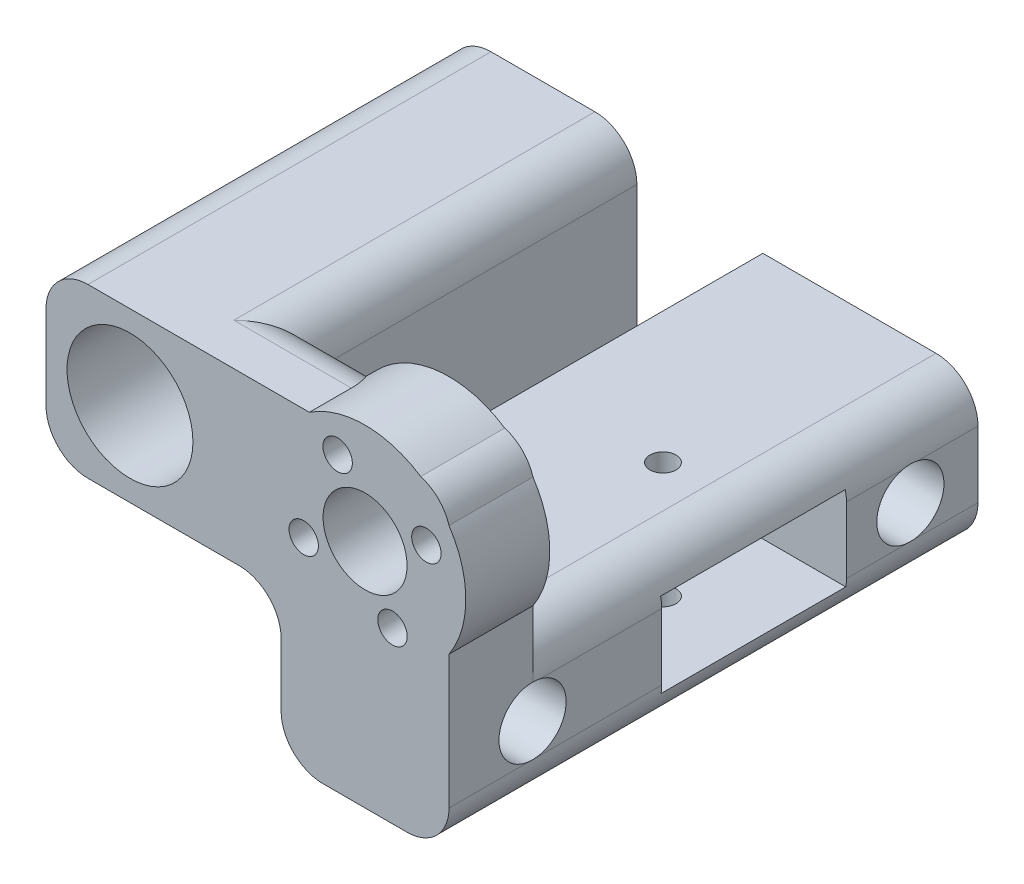
SolidWorks part; units mm, degrees
ref_plane "前视基准面" through (0, 0, 0) normal (0, 0, 1) x (1, 0, 0)
ref_plane "上视基准面" through (0, 0, 0) normal (0, 1, 0) x (1, 0, 0)
ref_plane "右视基准面" through (0, 0, 0) normal (1, 0, 0) x (0, 0, -1)
sketch "草图1" plane through (0, 0, 0) normal (0, 1, 0) x (1, 0, 0)
  line L1 (-10.5078, 7.8964) -> (37.4922, 7.8964)
  line L2 (-10.5078, 7.8964) -> (-10.5078, -40.1036)
  line L3 (-10.5078, -40.1036) -> (37.4922, -40.1036)
  line L4 (37.4922, 7.8964) -> (37.4922, -40.1036)
  line L5 (-10.5078, 7.8964) -> (37.4922, -40.1036) construction
  line L6 (-10.5078, -40.1036) -> (37.4922, 7.8964) construction
  point P4 (13.4922, -16.1036)
  dimension "D1" = 48
  dimension "D2" = 48
extrude "凸台-拉伸1" add sketch "草图1" along normal blind 40
sketch "草图2" plane through (0, 0, 40.1036) normal (0, 0, 1) x (1, 0, 0)
  line L0 (-10.5078, 40) -> (37.4922, 40) construction
  line L1 (-10.5078, 40) -> (-10.5078, 0) construction
  circle A0 centre (-0.5078, 30) radius 7.5
  circle A1 centre (27.4922, 30) radius 5
  circle A2 centre (24.2267, 37.3032) radius 1.75
  circle A3 centre (34.7954, 33.2656) radius 1.75
  circle A4 centre (20.1891, 26.7344) radius 1.75
  circle A5 centre (30.7578, 22.6968) radius 1.75
  dimension "D1" = 15
  dimension "D2" = 10
  dimension "D4" = 10
  dimension "D5" = 10
  dimension "D3" = 28
extrude "切除-拉伸1" cut sketch "草图2" against normal through all
sketch "草图3" plane through (0, 0, 40.1036) normal (0, 0, 1) x (1, 0, 0)
  circle A0 centre (27.4922, 30) radius 12
  circle A1 centre (27.4922, 30) radius 5.5
  circle A2 centre (24.2267, 37.3032) radius 1.75
  circle A3 centre (20.1891, 26.7344) radius 1.75
  circle A4 centre (30.7578, 22.6968) radius 1.75
  circle A5 centre (34.7954, 33.2656) radius 1.75
  dimension "D1" = 24
  dimension "D2" = 11
extrude "凸台-拉伸3" add sketch "草图3" against normal blind 10
sketch "草图4" plane through (0, 0, -7.8964) normal (0, 0, -1) x (-1, 0, 0)
  line L1 (-37.4922, 40) -> (-11.8688, 40)
  line L2 (-37.4922, 40) -> (-37.4922, 20.3994)
  line L3 (-37.4922, 20.3994) -> (-11.8688, 20.3994)
  line L4 (-11.8688, 40) -> (-11.8688, 20.3994)
  line L5 (-37.4922, 40) -> (-11.8688, 20.3994) construction
  line L6 (-37.4922, 20.3994) -> (-11.8688, 40) construction
  point P4 (-24.6805, 30.1997)
extrude "切除-拉伸2" cut sketch "草图4" against normal blind 38
fillet "圆角1" radius 5 1 edges at (37.4922, 40, 35.1036)
sketch "草图5" plane through (37.4922, 0, 0) normal (1, 0, 0) x (0, 0, -1)
  line L1 (-14.7696, 16.6006) -> (7.2304, 16.6006)
  line L2 (-14.7696, 16.6006) -> (-14.7696, 6.6006)
  line L3 (-14.7696, 6.6006) -> (7.2304, 6.6006)
  line L4 (7.2304, 16.6006) -> (7.2304, 6.6006)
  line L5 (-14.7696, 16.6006) -> (7.2304, 6.6006) construction
  line L18 (-14.7696, 6.6006) -> (7.2304, 16.6006) construction
  point P10 (0.3003, 11.5442)
  dimension "D1" = 10
  dimension "D2" = 22
extrude "切除-拉伸3" cut sketch "草图5" against normal through all
sketch "草图6" plane through (0, 0, 40.1036) normal (0, 0, 1) x (1, 0, 0)
  line L0 (37.4922, 0) -> (37.4922, 2.5)
  line L1 (37.4922, 23.3668) -> (37.4922, 0) construction
  line L2 (-7.5078, 2.5) -> (392.4922, 2.5) construction
  line L3 (37.4922, 2.5) -> (17.4922, 2.5)
  line L4 (17.4922, 2.5) -> (17.4922, 20)
  line L5 (17.4922, 20) -> (-10.5078, 20)
  line L6 (-10.5078, 40) -> (-10.5078, 0) construction
  line L7 (-10.5078, 20) -> (-10.5078, 0)
  line L8 (-10.5078, 0) -> (37.4922, 0)
  dimension "D1" = 20
  dimension "D2" = 20
extrude "切除-拉伸4" cut sketch "草图6" against normal through all
fillet "圆角2" radius 5 7 edges at (16.3639, 40, 30.1036) (11.8688, 40, 11.1036) (37.4922, 2.5, 16.1036) (-10.5078, 40, 16.1036) (-10.5078, 20, 16.1036) (17.4922, 2.5, 16.1036) (17.4922, 20, 16.1036)
sketch "草图7" plane through (17.4922, 0, 0) normal (-1, 0, 0) x (0, 0, 1)
  line L0 (-7.8964, 20) -> (-7.8964, 2.5)
  line L1 (-7.8964, 2.5) -> (1.8729, 2.5)
  line L2 (40.1036, 2.5) -> (-7.8964, 2.5) construction
  line L3 (1.8729, 2.5) -> (1.8729, 20)
  line L4 (40.1036, 20) -> (-7.8964, 20) construction
  line L5 (1.8729, 20) -> (-7.8964, 20)
extrude "凸台-拉伸4" add sketch "草图7" along normal blind 23
fillet "圆角3" radius 5 3 edges at (17.4922, 2.5, -3.0117) (-5.5078, 20, -3.0117) (-5.5078, 2.5, -3.0117)
fillet "圆角4" radius 5 1 edges at (37.4922, 20.3994, 11.1036)
sketch "草图8" plane through (0, 20.3994, 0) normal (0, 1, 0) x (1, 0, 0)
  line L0 (37.4107, -3.7696) -> (17.5738, -3.7696) construction
  line L5 (37.4107, -14.7696) -> (37.4107, 7.2304) construction
  line L6 (17.5738, 7.2304) -> (17.5738, -14.7696) construction
  circle A0 centre (27.4922, -4.6224) radius 1.55
  dimension "D1" = 3.1
extrude "切除-拉伸5" cut sketch "草图8" against normal through all
sketch "草图10" plane through (0, 2.5, 0) normal (0, -1, 0) x (1, 0, 0)
  circle A1 centre (27.4922, 4.6224) radius 1.55
  circle A2 centre (27.4922, 4.6224) radius 4
  dimension "D1" = 8
extrude "凸台-拉伸6" add sketch "草图10" along normal blind 3
sketch "草图11" plane through (0, 0, 1.8729) normal (0, 0, 1) x (1, 0, 0)
  line L0 (12.4922, 2.5) -> (22.4922, 2.5)
  line L1 (22.4922, 2.5) -> (17.4922, 7.5)
  line L2 (17.4922, 7.5) -> (12.4922, 2.5)
  arc A0 (17.4922, 7.5) -> (22.4922, 2.5) centre (22.4922, 7.5) ccw construction
  arc A1 (12.4922, 2.5) -> (17.4922, 7.5) centre (12.4922, 7.5) ccw construction
extrude "凸台-拉伸7" add sketch "草图11" against normal up to surface (9.7692 mm away) up to face at (10.4725, 17.6278, -7.8964)
sketch "草图14" plane through (37.4922, 0, 0) normal (1, 0, 0) x (0, 0, -1)
  circle A0 centre (-30.1576, 11.5) radius 4
  dimension "D1" = 8
extrude "切除-拉伸7" cut sketch "草图14" against normal through all
sketch "草图17" plane through (0, 0, -7.8964) normal (0, 0, -1) x (-1, 0, 0)
  line L0 (-11.8688, 20.3994) -> (-11.8688, 2.5)
  line L7 (-32.4922, 2.5) -> (0.5078, 2.5)
  line L8 (5.5078, 7.5) -> (5.5078, 16.3397)
  line L9 (10.5078, 25) -> (10.5078, 35)
  line L10 (5.5078, 40) -> (-6.8688, 40)
  line L11 (-11.8688, 35) -> (-11.8688, 20.3994)
  line L12 (-11.8688, 20.3994) -> (-32.4922, 20.3994)
  line L13 (-37.4922, 15.3994) -> (-37.4922, 7.5)
  line L14 (-32.4922, 2.5) -> (-11.8688, 2.5)
  line L19 (-11.8688, 20.3994) -> (-32.4922, 20.3994)
  line L20 (-37.4922, 15.3994) -> (-37.4922, 7.5)
  arc A7 (0.5078, 2.5) -> (5.5078, 7.5) centre (0.5078, 7.5) ccw
  arc A8 (8.0078, 20.6699) -> (5.5078, 16.3397) centre (10.5078, 16.3397) ccw
  arc A9 (8.0078, 20.6699) -> (10.5078, 25) centre (5.5078, 25) ccw
  arc A10 (10.5078, 35) -> (5.5078, 40) centre (5.5078, 35) ccw
  arc A11 (-6.8688, 40) -> (-11.8688, 35) centre (-6.8688, 35) ccw
  arc A12 (-32.4922, 20.3994) -> (-37.4922, 15.3994) centre (-32.4922, 15.3994) ccw
  arc A13 (-37.4922, 7.5) -> (-32.4922, 2.5) centre (-32.4922, 7.5) ccw
  arc A19 (-32.4922, 20.3994) -> (-37.4922, 15.3994) centre (-32.4922, 15.3994) ccw
  arc A20 (-37.4922, 7.5) -> (-32.4922, 2.5) centre (-32.4922, 7.5) ccw
  dimension "D1" = 0
extrude "凸台-拉伸8" add sketch "草图17" along normal blind 15
sketch "草图18" plane through (11.8688, 0, 0) normal (-1, 0, 0) x (0, 0, 1)
  circle A0 centre (-14.8424, 11.5) radius 4
extrude "切除-拉伸10" cut sketch "草图18" against normal through all
sketch "草图16" plane through (37.4922, 0, 0) normal (1, 0, 0) x (0, 0, -1)
  circle A0 centre (14.8424, 11.5) radius 4
extrude "切除-拉伸8" cut sketch "草图16" against normal through all rebuild error yes
